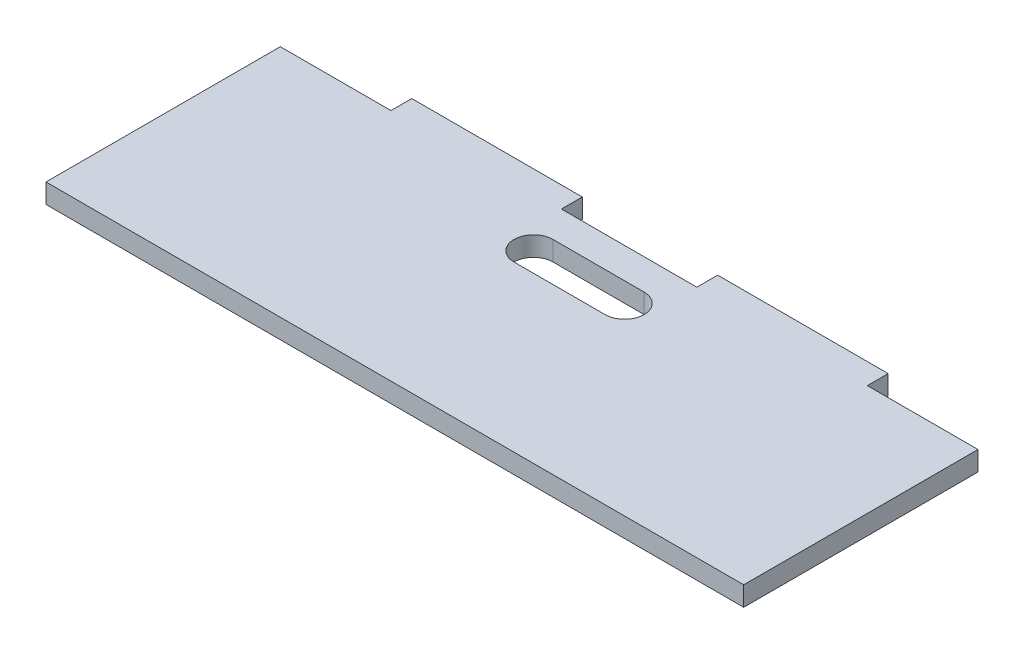
SolidWorks part; units mm, degrees
ref_plane "Front Plane" through (0, 0, 0) normal (0, 0, 1) x (1, 0, 0)
ref_plane "Top Plane" through (0, 0, 0) normal (0, 1, 0) x (1, 0, 0)
ref_plane "Right Plane" through (0, 0, 0) normal (1, 0, 0) x (0, 0, -1)
sketch "Sketch1" plane through (0, 0, 0) normal (0, 1, 0) x (1, 0, 0)
  line L0 (0, 18) -> (8.5, 18)
  line L1 (0, 0) -> (53.6, 0)
  line L5 (8.5, 18) -> (8.5, 19.6)
  line L6 (8.5, 19.6) -> (21.6, 19.6)
  line L7 (21.6, 19.6) -> (21.6, 18)
  line L8 (21.6, 18) -> (32, 18)
  line L9 (32, 18) -> (32, 19.6)
  line L10 (32, 19.6) -> (45.1, 19.6)
  line L11 (45.1, 19.6) -> (45.1, 18)
  line L12 (45.1, 18) -> (53.6, 18)
  line L13 (53.6, 18) -> (53.6, 0)
  line L14 (0, 0) -> (0, 18)
  line L15 (23.3, 14.15) -> (30.3, 14.15) construction
  line L16 (23.3, 15.65) -> (30.3, 15.65)
  line L17 (23.3, 12.65) -> (30.3, 12.65)
  arc A0 (23.3, 15.65) -> (23.3, 12.65) centre (23.3, 14.15) ccw
  arc A1 (30.3, 12.65) -> (30.3, 15.65) centre (30.3, 14.15) ccw
  point P7 (26.8, 14.15)
  point P20 (21.8, 14.15)
  point P21 (31.8, 14.15)
  point P22 (0, 0)
  point P23 (0, 0)
  point P24 (0, 0)
  point P25 (26.8, 0)
  dimension "D1" = 53.6
  dimension "D2" = 1.6
  dimension "D4" = 8.5
  dimension "D5" = 10.4
  dimension "D6" = 13.1
  dimension "D7" = 3
  dimension "D8" = 10
  dimension "D9" = 5.35
  dimension "D3" = 18
extrude "Boss-Extrude1" add sketch "Sketch1" along normal blind 1.5
equation "\"margin\"= 0.2"
equation "\"height\"= 18"
equation "\"length\"= 113"
equation "\"tabwidth\"= 10"
equation "\"D4@Sketch1\"= \"tabwidth\" + \"margin\" - \"thick\" - \"margin\""
equation "\"D5@Sketch1\"=\"tabwidth\"+(2*\"margin\")"
equation "\"D3@Sketch1\"=\"height\""
equation "\"width\"= 57"
equation "\"D1@Sketch1\" = \"width\" - 2 * ( \"thick\" + \"margin\" )"
equation "\"thick\"= 1.5"
equation "\"D2@Sketch1\"=\"thick\"+(\"margin\"/2)"
equation "\"D1@Boss-Extrude1\"=\"thick\""
